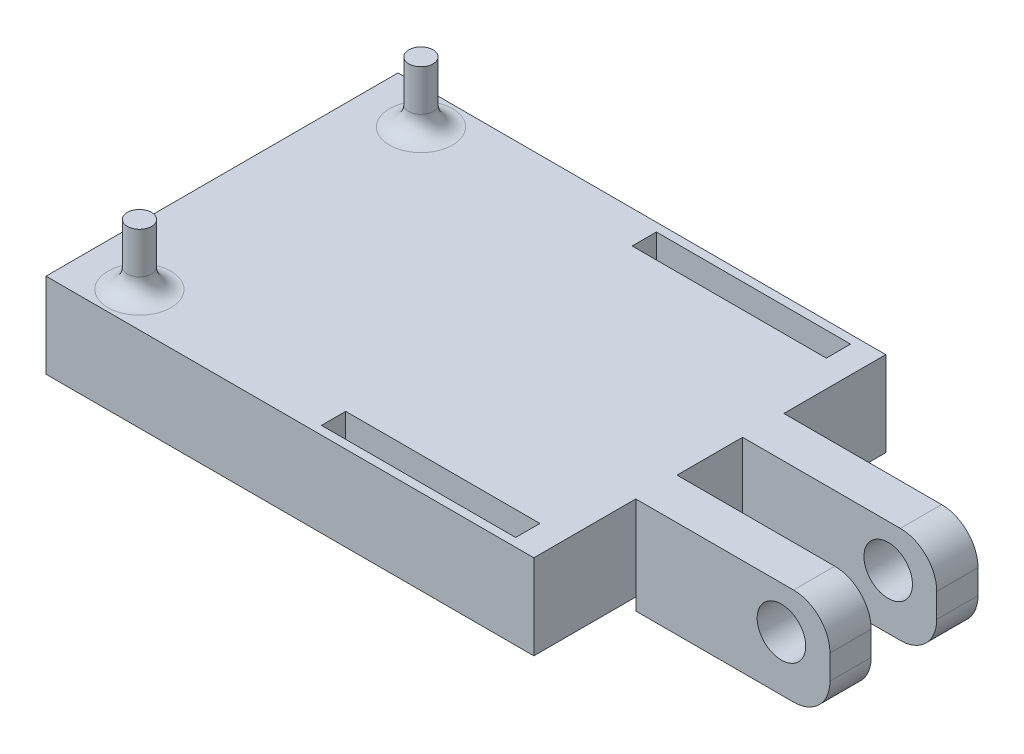
SolidWorks part; units mm, degrees
material "Beryllium Copper, UNS C17000"
ref_plane "Front Plane" through (0, 0, 0) normal (0, 0, 1) x (1, 0, 0)
ref_plane "Top Plane" through (0, 0, 0) normal (0, 1, 0) x (1, 0, 0)
ref_plane "Right Plane" through (0, 0, 0) normal (1, 0, 0) x (0, 0, -1)
sketch "Sketch1" plane through (0, 0, 0) normal (0, 1, 0) x (1, 0, 0)
  line L1 (-25.4, 18.415) -> (25.4, 18.415)
  line L2 (-25.4, 18.415) -> (-25.4, -18.415)
  line L3 (-25.4, -18.415) -> (25.4, -18.415)
  line L4 (25.4, 18.415) -> (25.4, -18.415)
  line L5 (-25.4, 18.415) -> (25.4, -18.415) construction
  line L6 (-25.4, -18.415) -> (25.4, 18.415) construction
  point P0 (0, 0)
  point P6 (0, 18.415)
  point P7 (0, -18.415)
  dimension "D1" = 50.8
  dimension "D2" = 36.83
extrude "Boss-Extrude1" add sketch "Sketch1" against normal blind 8.89 separate body
sketch "Sketch2" plane through (25.4, 0, 0) normal (1, 0, 0) x (0, 0, -1)
  line L13 (-18.415, 0) -> (18.415, 0)
  line L14 (-18.415, 0) -> (-18.415, -8.89)
  line L15 (-18.415, -8.89) -> (18.415, -8.89)
  line L17 (18.415, 0) -> (18.415, -8.89)
extrude "Boss-Extrude2" add sketch "Sketch2" along normal blind 0.254
sketch "Sketch3" plane through (25.654, 0, 0) normal (1, 0, 0) x (0, 0, -1)
  line L1 (-7.747, 0) -> (-3.429, 0)
  line L2 (-7.747, 0) -> (-7.747, -10.16)
  line L3 (-7.747, -10.16) -> (-3.429, -10.16)
  line L4 (-3.429, 0) -> (-3.429, -10.16)
  line L5 (-7.747, 0) -> (-3.429, -10.16) construction
  line L6 (-7.747, -10.16) -> (-3.429, 0) construction
  line L7 (3.429, 0) -> (7.747, 0)
  line L8 (3.429, 0) -> (3.429, -10.16)
  line L9 (3.429, -10.16) -> (7.747, -10.16)
  line L10 (7.747, 0) -> (7.747, -10.16)
  line L11 (3.429, 0) -> (7.747, -10.16) construction
  line L12 (3.429, -10.16) -> (7.747, 0) construction
  line L13 (-18.415, 0) -> (-18.415, -8.89) construction
  line L14 (-18.415, 0) -> (-18.415, -8.89)
  line L15 (-5.588, -5.08) -> (5.588, -5.08) construction
  point P0 (-5.588, -5.08)
  point P5 (5.588, -5.08)
  point P10 (0, -5.08)
  point P21 (-5.588, 0)
  dimension "D1" = 4.318
  dimension "D2" = 6.858
  dimension "D3" = 10.16
extrude "Boss-Extrude3" add sketch "Sketch3" along normal blind 20.32 contours L4 L3 L2 L1 | L10 L9 L8 L7
sketch "Sketch4" plane through (0, 0, -7.747) normal (0, 0, -1) x (-1, 0, 0)
  line L0 (-25.654, -8.89) -> (-25.654, 0) construction
  line L1 (-45.974, 0) -> (-25.654, 0) construction
  line L2 (-25.654, -8.89) -> (-25.654, 0)
  line L3 (-45.974, 0) -> (-25.654, 0)
  line L4 (-45.974, 0) -> (-45.974, -10.16) construction
  circle A0 centre (-40.894, -4.445) radius 2.54
  point P9 (-25.654, -4.445)
  dimension "D1" = 5.08
  dimension "D2" = 5.08
extrude "Cut-Extrude1" cut sketch "Sketch4" against normal through all both and the other way through all contours A0
fillet "Fillet1" radius 3.81 4 edges at (45.974, 0, 5.588) (45.974, -10.16, 5.588) (45.974, 0, -5.588) (45.974, -10.16, -5.588)
sketch "Sketch7" plane through (0, 0, 0) normal (0, 1, 0) x (1, 0, 0)
  line L1 (-22.352, 17.78) -> (22.352, 17.78)
  line L2 (-22.352, 17.78) -> (-22.352, -17.78)
  line L3 (-22.352, -17.78) -> (22.352, -17.78)
  line L4 (22.352, 17.78) -> (22.352, -17.78)
  line L5 (-22.352, 17.78) -> (22.352, -17.78) construction
  line L6 (-22.352, -17.78) -> (22.352, 17.78) construction
  line L7 (2.54, -14.986) -> (22.86, -14.986)
  line L8 (2.54, -14.986) -> (2.54, -17.526)
  line L9 (2.54, -17.526) -> (22.86, -17.526)
  line L10 (22.86, -14.986) -> (22.86, -17.526)
  line L11 (2.54, -14.986) -> (22.86, -17.526) construction
  line L12 (2.54, -17.526) -> (22.86, -14.986) construction
  line L13 (2.54, 17.526) -> (22.86, 17.526)
  line L14 (2.54, 17.526) -> (2.54, 14.986)
  line L15 (2.54, 14.986) -> (22.86, 14.986)
  line L16 (22.86, 17.526) -> (22.86, 14.986)
  line L17 (2.54, 17.526) -> (22.86, 14.986) construction
  line L18 (2.54, 14.986) -> (22.86, 17.526) construction
  circle A0 centre (-19.304, -14.732) radius 1.27
  circle A1 centre (-19.304, 14.732) radius 1.27
  point P0 (0, 0)
  point P10 (12.7, -16.256)
  point P15 (12.7, 16.256)
  dimension "D3" = 3.048
  dimension "D4" = 3.048
  dimension "D6" = 2.54
  dimension "D7" = 2.54
  dimension "D8" = 3.048
  dimension "D1" = 44.704
  dimension "D2" = 35.56
  dimension "D5" = 29.464
  dimension "D11" = 2.54
  dimension "D12" = 2.54
  dimension "D13" = 20.32
  dimension "D14" = 20.32
  dimension "D15" = 0.254
  dimension "D16" = 0.254
extrude "Cut-Extrude2" cut sketch "Sketch18<5>" against normal through all contours L15 L16 L13 L14
sketch "Sketch18<5>" plane through (0, 0, 0) normal (0, 1, 0) x (1, 0, 0) same geometry as "Sketch7"
extrude "Cut-Extrude3" cut sketch "Sketch7" against normal through all contours L9 L10 L7 L8
extrude "Boss-Extrude4" add sketch "Sketch18<16>" along normal blind 6.35 contours A0 | A1
sketch "Sketch18<16>" plane through (0, 0, 0) normal (0, 1, 0) x (1, 0, 0) same geometry as "Sketch7"
fillet "Fillet2" radius 2.032 2 edges at (-19.304, 0, -13.462) (-19.304, 0, 16.002)
